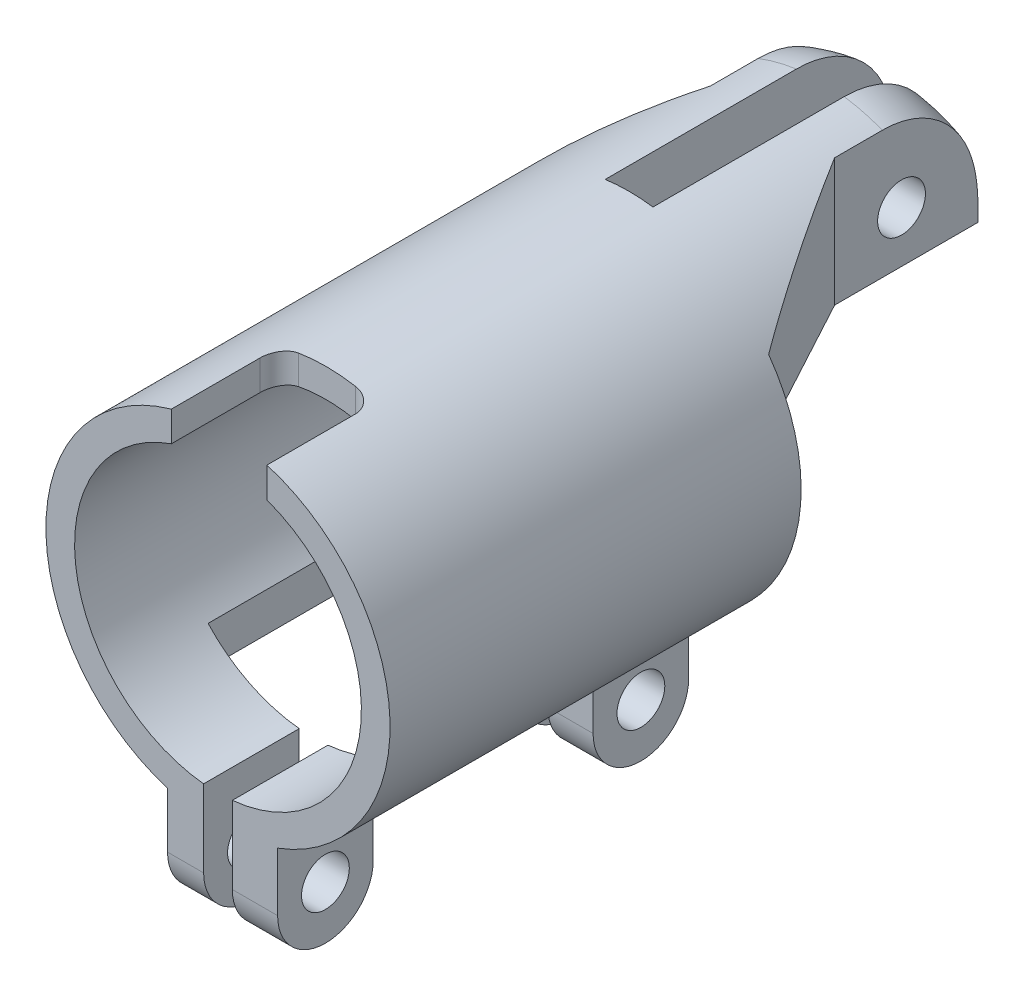
SolidWorks part; units mm, degrees
ref_plane "前视" through (0, 0, 0) normal (0, 0, 1) x (1, 0, 0)
ref_plane "上视" through (0, 0, 0) normal (0, 1, 0) x (1, 0, 0)
ref_plane "右视" through (0, 0, 0) normal (1, 0, 0) x (0, 0, -1)
sketch "Sketch1" plane through (0, 0, 0) normal (0, 0, 1) x (1, 0, 0)
  line L1 (11.035, -27) -> (-11.035, -27)
  line L2 (11.035, -27) -> (11.035, -3)
  line L3 (11.035, -3) -> (-11.035, -3)
  line L4 (-11.035, -27) -> (-11.035, -3)
  line L5 (11.035, -27) -> (-11.035, -3) construction
  line L6 (11.035, -3) -> (-11.035, -27) construction
  line L7 (6.2374, -28) -> (-6.2374, -28)
  line L8 (6.2374, -28) -> (6.2374, -2)
  line L9 (6.2374, -2) -> (-6.2374, -2)
  line L10 (-6.2374, -28) -> (-6.2374, -2)
  line L11 (6.2374, -28) -> (-6.2374, -2) construction
  line L12 (6.2374, -2) -> (-6.2374, -28) construction
  line L13 (1.5, -28) -> (-1.5, -28)
  line L14 (1.5, -28) -> (1.5, -2)
  line L15 (1.5, -2) -> (-1.5, -2)
  line L16 (-1.5, -28) -> (-1.5, -2)
  line L17 (1.5, -28) -> (-1.5, -2) construction
  line L18 (1.5, -2) -> (-1.5, -28) construction
  line L19 (20.2532, -3.4361) -> (-20.2532, -3.4361)
  line L20 (20.2532, -3.4361) -> (20.2532, 3.4361)
  line L21 (20.2532, 3.4361) -> (-20.2532, 3.4361)
  line L22 (-20.2532, -3.4361) -> (-20.2532, 3.4361)
  line L23 (20.2532, -3.4361) -> (-20.2532, 3.4361) construction
  line L24 (20.2532, 3.4361) -> (-20.2532, -3.4361) construction
  circle A0 centre (0, 0) radius 15
  circle A1 centre (0, 0) radius 18
  point P4 (0, -15)
  point P5 (0, -14.5)
  point P10 (0, -15)
  point P15 (0, -15)
  dimension "D1" = 30
  dimension "D2" = 36
  dimension "D3" = 24
  dimension "D4" = 26
  dimension "D5" = 3
extrude "Boss-Extrude1" add sketch "Sketch1" along normal blind 7 contours L8 A1 L2 A0 | A1 L14 L1 L8 | L14 L7 L8 L1 | A1 L10 L1 L16 | L7 L16 L1 L10 | L21 A1 L19 A0 | L19 A1 L4 A0 | L19 A1 L21 A0 | L2 A1 L19 A0 | L14 A1 L8 A0 | L10 A1 L16 A0 | L4 A1 L10 A0 | L21 A1 A0 region at (3.8687, -27.5, 0) region at (3.9124, -22.2567, 0) region at (8.7249, -13.872, 0) region at (14.1331, -8.2064, 0) region at (3.8976, -15.9659, 0) region at (16.3782, 0, 0) region at (-3.8687, -27.5, 0) region at (-3.9124, -22.2567, 0) region at (-3.8976, -15.9659, 0) region at (16.1351, 3.8183, 0) region at (-8.7249, -13.872, 0) region at (-16.3782, 0, 0) region at (-14.1331, -8.2064, 0)
extrude "Boss-Extrude2" add sketch "Sketch1<3>" along normal blind 30 contours L21 A1 L19 A0 | L19 A1 L4 A0 | L2 A1 L19 A0 | L19 A1 L21 A0 | L21 A1 A0 region at (14.1331, -8.2064, 0) region at (16.3782, 0, 0) region at (16.1351, 3.8183, 0) region at (-16.3782, 0, 0) region at (-14.1331, -8.2064, 0)
sketch "Sketch1<3>" plane through (0, 0, 0) normal (0, 0, 1) x (1, 0, 0) same geometry as "Sketch1"
sketch "Sketch2" plane through (0, 0, 30) normal (0, 0, 1) x (1, 0, 0)
  line L0 (-5.2778, -28) -> (6.2374, -28)
  line L1 (-5.2778, -28) -> (-5.2778, -14.1291)
  line L2 (6.2374, -28) -> (6.2374, -14.1291)
  line L3 (-5.2778, -14.1291) -> (6.2374, -14.1291)
  line L4 (-1.5, -28) -> (-6.2374, -28) construction
  line L5 (1.5, -28) -> (-1.5, -28)
  line L6 (1.5, -28) -> (1.5, -11.0389)
  line L7 (-1.5, -28) -> (-1.5, -11.0389)
  line L8 (1.5, -11.0389) -> (-1.5, -11.0389)
  circle A0 centre (0, 0) radius 15
  circle A1 centre (0, 0) radius 18
  arc M1 (-11.035, -10.1602) -> (11.035, -10.1602) centre (0, 0) cw
  line M2 (11.035, -10.1602) -> (11.035, -14.2207)
  arc M3 (11.035, -14.2207) -> (-11.035, -14.2207) centre (0, 0) ccw
  line M4 (-11.035, -14.2207) -> (-11.035, -10.1602)
extrude "Boss-Extrude3" add sketch "Sketch2" along normal blind 10 contours M4 M1 M2 M3 | A1 L1 L3 A0 M4 | L2 A1 A0 L3 M2 | L6 A1 L2 L3 A0 | A1 L6 L0 L2 | A1 L1 L0 L7 | L1 A1 L7 A0 L3 region at (-3.411, -22.8194, 30) region at (-8.2718, -14.1121, 30) region at (-3.403, -16.1045, 30) region at (3.9082, -22.7572, 30) region at (-7.7049, 15.7314, 30) region at (3.8597, -16.0048, 30) region at (8.6784, -13.8736, 30)
sketch "Sketch3" plane through (0, 0, 0) normal (0, 1, 0) x (1, 0, 0)
  line L1 (5.1192, -53.7088) -> (-4.8808, -53.7088)
  line L2 (5.1192, -53.7088) -> (5.1192, -30.7088)
  line L3 (3.1192, -28.7088) -> (-2.8808, -28.7088)
  line L4 (-4.8808, -53.7088) -> (-4.8808, -30.7088)
  line L5 (5.1192, -53.7088) -> (-4.8808, -28.7088) construction
  line L6 (5.1192, -28.7088) -> (-4.8808, -53.7088) construction
  arc A0 (5.1192, -30.7088) -> (3.1192, -28.7088) centre (3.1192, -30.7088) ccw
  arc A1 (-4.8808, -30.7088) -> (-2.8808, -28.7088) centre (-2.8808, -30.7088) cw
  point P0 (0.1192, -41.2088)
  dimension "D3" = 2
  dimension "D1" = 10
  dimension "D2" = 25
extrude "Cut-Extrude1" cut sketch "Sketch3" along normal through all
extrude "Boss-Extrude4" add sketch "Sketch1<4>" against normal blind 3 contours L14 L7 L8 L1 | L7 L16 L1 L10 | A1 L10 L1 L16 | A1 L14 L1 L8 | L14 A1 L8 A0 | L10 A1 L16 A0 | L4 A1 L10 A0 | L19 A1 L4 A0 | L21 A1 L19 A0 | L21 A1 A0 | L19 A1 L21 A0 | L2 A1 L19 A0 | L8 A1 L2 A0 | L21 A0 region at (3.8687, -27.5, 0) region at (3.9124, -22.2567, 0) region at (8.7249, -13.872, 0) region at (14.1331, -8.2064, 0) region at (3.8976, -15.9659, 0) region at (16.3782, 0, 0) region at (-3.8687, -27.5, 0) region at (-3.9124, -22.2567, 0) region at (-3.8976, -15.9659, 0) region at (16.1351, 3.8183, 0) region at (-8.7249, -13.872, 0) region at (0, 8.2595, 0) region at (-16.3782, 0, 0) region at (-14.1331, -8.2064, 0)
sketch "Sketch1<4>" plane through (0, 0, 0) normal (0, 0, 1) x (1, 0, 0) same geometry as "Sketch1"
ref_point "Point1"
ref_point "Point2"
sketch "Sketch5" plane through (6.2374, 0, 0) normal (1, 0, 0) x (0, 0, -1)
  circle A0 centre (-35, -22.4424) radius 2.5
  circle A1 centre (-2, -22.4424) radius 2.5
extrude "Cut-Extrude2" cut sketch "Sketch5" against normal through all
sketch "Sketch7" plane through (0, 0, -3) normal (0, 0, -1) x (-1, 0, 0)
  line L0 (-14.6011, 3.4361) -> (14.6011, 3.4361) construction
  line L1 (2.5, -19.7328) -> (-2.5, -19.7328)
  line L2 (2.5, -19.7328) -> (2.5, 19.7328)
  line L3 (2.5, 19.7328) -> (-2.5, 19.7328)
  line L4 (-2.5, -19.7328) -> (-2.5, 19.7328)
  line L5 (2.5, -19.7328) -> (-2.5, 19.7328) construction
  line L6 (2.5, 19.7328) -> (-2.5, -19.7328) construction
  line L7 (6.5, -19.7328) -> (-6.5, -19.7328)
  line L8 (6.5, -19.7328) -> (6.5, 19.7328)
  line L9 (6.5, 19.7328) -> (-6.5, 19.7328)
  line L10 (-6.5, -19.7328) -> (-6.5, 19.7328)
  line L11 (6.5, -19.7328) -> (-6.5, 19.7328) construction
  line L12 (6.5, 19.7328) -> (-6.5, -19.7328) construction
  line L13 (6.5, -3.4361) -> (-6.5, -3.4361)
  line L14 (6.5, -3.4361) -> (6.5, 3.4361)
  line L15 (6.5, 3.4361) -> (-6.5, 3.4361)
  line L16 (-6.5, -3.4361) -> (-6.5, 3.4361)
  line L17 (6.5, -3.4361) -> (-6.5, 3.4361) construction
  line L18 (6.5, 3.4361) -> (-6.5, -3.4361) construction
  circle A0 centre (0, 0) radius 18
  point P0 (0, 0)
  point P6 (0, 0)
  line M3 (-14.6011, 3.4361) -> (14.6011, 3.4361)
  arc M8 (6.2374, -16.8848) -> (-6.2374, -16.8848) centre (0, 0) ccw
  dimension "D1" = 5
  dimension "D2" = 13
extrude "Boss-Extrude5" add sketch "Sketch7" along normal blind 30 contours L10 L4 M3 M8 | L8 L2 M3 M8 region at (-4.4752, 10.4151, -3) region at (4.4752, 10.4151, -3)
fillet "Fillet1" radius 10 2 edges at (-4.53, 17.4207, -33) (4.53, 17.4207, -33)
sketch "Sketch8" plane through (6.5, 0, 0) normal (1, 0, 0) x (0, 0, -1)
  line L0 (23, 16.7854) -> (3, 16.7854) construction
  line L1 (33, 3.4361) -> (33, 4.6637) construction
  circle A0 centre (25, 8.7854) radius 2.5
  point P0 (25, 8.7854)
  dimension "D1" = 8
  dimension "D2" = 8
extrude "Cut-Extrude3" cut sketch "Sketch8" against normal through all
fillet "Fillet2" radius 5 6 edges at (-3.8687, -28, 7) (-3.8687, -28, -3) (3.8687, -28, -3) (3.8687, -28, 30) (-3.3889, -28, 40) (3.8687, -28, 40)
sketch "Sketch9" plane through (0, 3.4361, 0) normal (0, -1, 0) x (1, 0, 0)
  line L0 (6.5, -3) -> (6.5, -18)
  line L1 (6.5, -33) -> (6.5, -3) construction
  line L2 (6.5, -18) -> (14.6011, -3)
  line L3 (14.6011, -3) -> (6.5, -3)
  line L4 (-6.5, -3) -> (-6.5, -18)
  line L5 (-6.5, -33) -> (-6.5, -3) construction
  line L6 (-6.5, -18) -> (-14.6011, -3)
  line L7 (-14.6011, -3) -> (-6.5, -3)
extrude "Boss-Extrude6" add sketch "Sketch9" against normal blind 15
sketch "Sketch10" plane through (0, 0, -3) normal (0, 0, -1) x (-1, 0, 0)
  circle A0 centre (0, 0) radius 18
  circle A1 centre (0, 0) radius 29.5351
extrude "Cut-Extrude4" cut sketch "Sketch10" along normal through all
